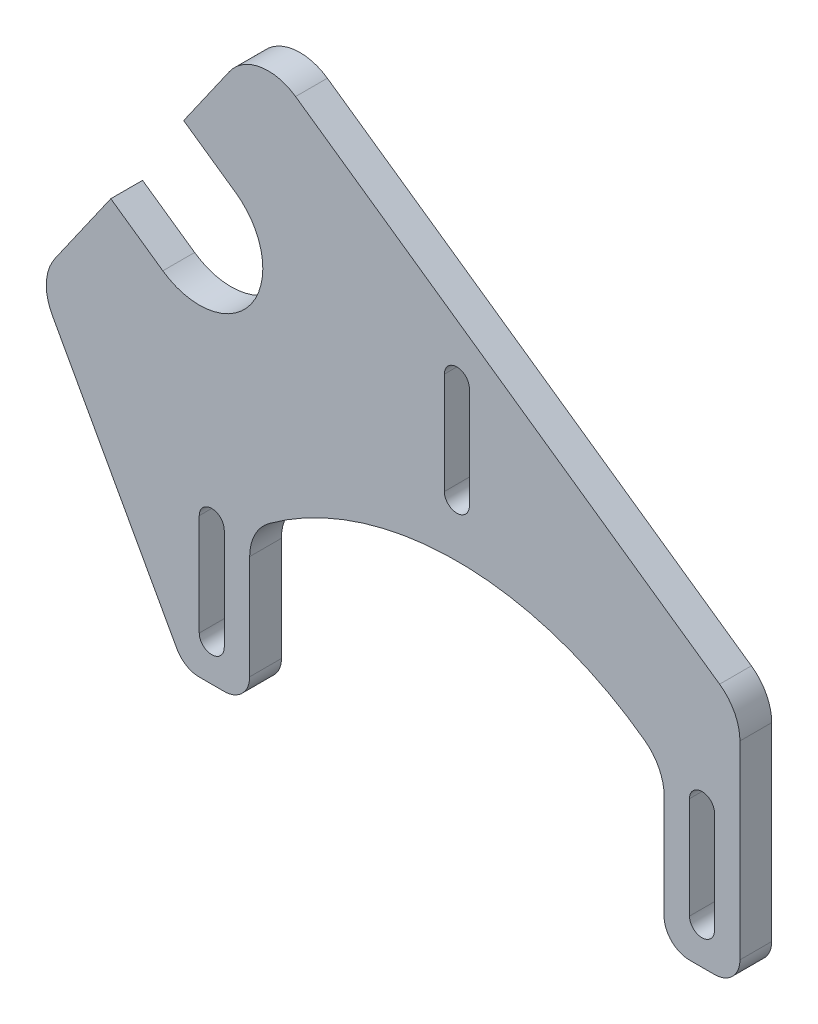
SolidWorks part; units mm, degrees
ref_plane "Front" through (0, 0, 0) normal (0, 0, 1) x (1, 0, 0)
ref_plane "Top" through (0, 0, 0) normal (0, 1, 0) x (1, 0, 0)
ref_plane "Right" through (0, 0, 0) normal (1, 0, 0) x (0, 0, -1)
sketch "Sketch1" plane through (0, 0, 0) normal (0, 0, 1) x (1, 0, 0)
  line L0 (-46.5, 0) -> (-46.5, -31.205) construction
  line L1 (-41.42, 12.7) -> (-41.42, -12.7)
  line L2 (46.5, 0) -> (46.5, -31.205) construction
  line L3 (-46.5, 0) -> (46.5, 0) construction
  line L4 (41.42, -12.7) -> (41.42, 12.7)
  line L5 (0, 61.7) -> (0, 36.3) construction
  line L6 (-54.6116, 76.999) -> (-44.2083, 69.7146)
  line L7 (-58.7772, 48.9081) -> (-69.1804, 56.1926)
  line L8 (-69.1804, 56.1926) -> (-54.6116, 76.999) construction
  line L9 (-46.5, -17.78) -> (-51.5, -17.78)
  line L10 (-83.7492, 35.3861) -> (-69.1804, 56.1926)
  line L11 (-54.6116, 76.999) -> (-40.0427, 97.8055)
  line L12 (-106.3912, -19.0917) -> (3.4057, 137.7145) construction
  line L13 (56.58, -12.7) -> (56.58, 30.1495)
  line L14 (-59.5056, 47.8678) -> (-43.4799, 70.7549) construction
  line L15 (46.5, -17.78) -> (51.5, -17.78)
  line L18 (51.5, -17.78) -> (51.5, 0) construction
  line L19 (-40.0427, 97.8055) -> (56.58, 30.1495)
  line L20 (-51.5, 0) -> (-51.5, -17.78) construction
  line L21 (-55.951, -15.1484) -> (-83.7492, 35.3861)
  circle A0 centre (49, 0) radius 2.5 construction
  arc A1 (51.5, -17.78) -> (56.58, -12.7) centre (51.5, -12.7) ccw
  arc A2 (-41.42, 12.7) -> (41.42, 12.7) centre (0, -35.4314) cw
  arc A4 (-51.5, -17.78) -> (-55.951, -15.1484) centre (-51.5, -12.7) cw
  circle A6 centre (49, 0) radius 2.5 construction
  circle A7 centre (-49, 0) radius 2.5 construction
  arc A8 (39.8609, -39.3333) -> (-39.8609, -39.3333) centre (0, 0) ccw construction
  circle A11 centre (0, 49) radius 2.5 construction
  circle A12 centre (-51.4928, 59.3114) radius 12.7 construction
  arc A15 (-44.2083, 69.7146) -> (-58.7772, 48.9081) centre (-51.4928, 59.3114) cw
  arc A16 (-41.42, -12.7) -> (-46.5, -17.78) centre (-46.5, -12.7) cw
  arc A18 (41.42, -12.7) -> (46.5, -17.78) centre (46.5, -12.7) ccw
  point P3 (-49, 0)
  point P16 (-41.42, 0)
  point P19 (41.42, 0)
  point P23 (0, 49)
  dimension "D1" = 5.08
  dimension "D4" = 5.08
  dimension "D6" = 63.5
  dimension "D2" = 5.08
  dimension "D3" = 25.4
  dimension "D5" = 25.4
extrude "Extrude1" add sketch "Sketch1" along normal blind 6.35
sketch "Sketch4" plane through (0, 0, 6.35) normal (0, 0, 1) x (1, 0, 0)
  line L0 (-51.5, -10.16) -> (-51.5, 10.16)
  line L1 (-46.5, -10.16) -> (-46.5, 10.16)
  line L2 (-51.5, 0) -> (-46.5, 0) construction
  line L3 (2.5, 38.84) -> (2.5, 59.16)
  line L4 (-2.5, 38.84) -> (-2.5, 59.16)
  line L5 (2.5, 49) -> (-2.5, 49) construction
  line L6 (51.5, -10.16) -> (51.5, 10.16)
  line L7 (46.5, -10.16) -> (46.5, 10.16)
  line L8 (46.5, 0) -> (51.5, 0) construction
  line L9 (-51.4928, 59.3114) -> (0, -36) construction
  line L10 (-51.4928, 59.3114) -> (-34.6579, 83.354) construction
  line L11 (-59.5056, 47.8678) -> (-43.4799, 70.7549) construction
  circle A0 centre (0, 49) radius 2.5 construction
  circle A1 centre (49, 0) radius 2.5 construction
  circle A2 centre (-49, 0) radius 2.5 construction
  circle A3 centre (-49, 0) radius 2.5 construction
  circle A4 centre (0, 49) radius 2.5 construction
  arc A5 (-51.5, 10.16) -> (-46.5, 10.16) centre (-49, 10.16) cw
  circle A6 centre (49, 0) radius 2.5 construction
  arc A7 (-51.5, -10.16) -> (-46.5, -10.16) centre (-49, -10.16) ccw
  arc A8 (-2.5, 59.16) -> (2.5, 59.16) centre (0, 59.16) cw
  arc A9 (-2.5, 38.84) -> (2.5, 38.84) centre (0, 38.84) ccw
  arc A10 (46.5, 10.16) -> (51.5, 10.16) centre (49, 10.16) cw
  arc A11 (46.5, -10.16) -> (51.5, -10.16) centre (49, -10.16) ccw
  circle A12 centre (0, -36) radius 6.35 construction
  arc A13 (-58.7772, 48.9081) -> (-44.2083, 69.7146) centre (-51.4928, 59.3114) ccw construction
  dimension "D1" = 5
  dimension "D2" = 116.619
  dimension "D3" = 20.32
extrude "Cut-Extrude3" cut sketch "Sketch4" against normal up to next
fillet "Fillet1" radius 9.525 5 edges at (56.58, 30.1495, 3.175) (41.42, 12.7, 3.175) (-41.42, 12.7, 3.175) (-83.7492, 35.3861, 3.175) (-40.0427, 97.8055, 3.175)
